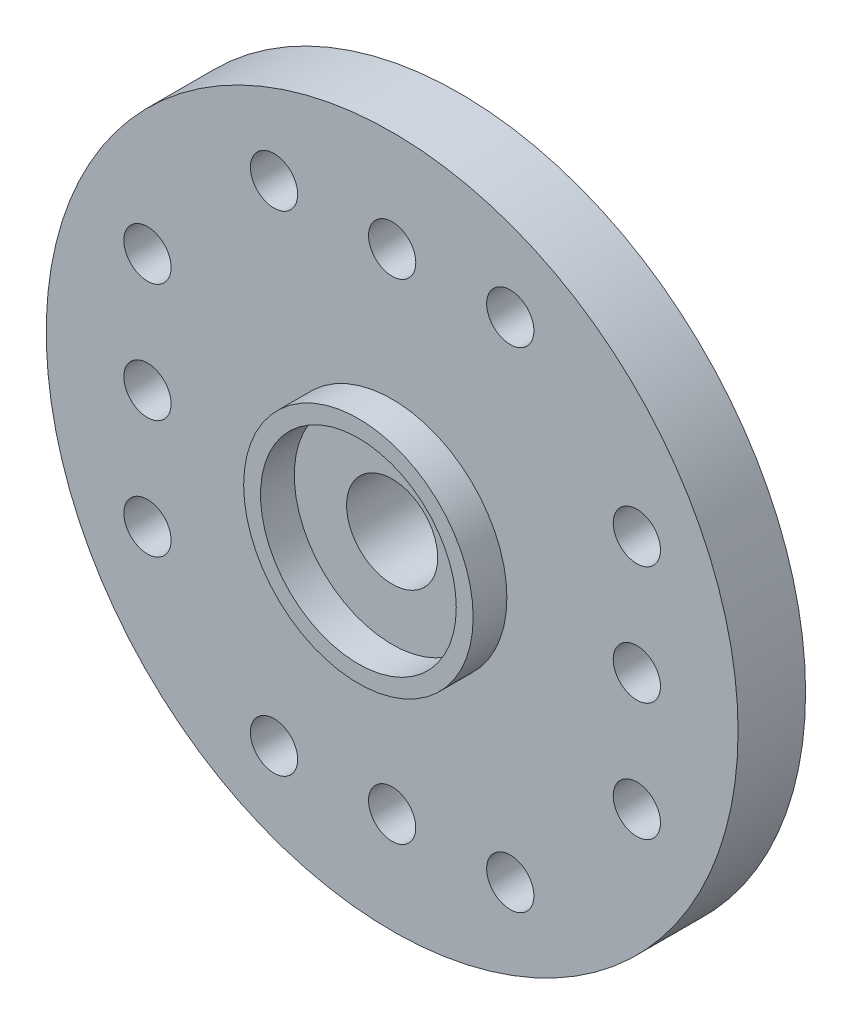
SolidWorks part; units mm, degrees
ref_plane "Front Plane" through (0, 0, 0) normal (0, 0, 1) x (1, 0, 0)
ref_plane "Top Plane" through (0, 0, 0) normal (0, 1, 0) x (1, 0, 0)
ref_plane "Right Plane" through (0, 0, 0) normal (1, 0, 0) x (0, 0, -1)
sketch "Sketch1" plane through (0, 0, 0) normal (0, 0, 1) x (1, 0, 0)
  circle A0 centre (0, 0) radius 10.25
  dimension "D1" = 20.5
extrude "Boss-Extrude1" add sketch "Sketch1" along normal blind 2
sketch "Sketch2" plane through (0, 0, 2) normal (0, 0, 1) x (1, 0, 0)
  circle A0 centre (0, 0) radius 3.4
  circle A1 centre (0, 0) radius 2.9
  dimension "D1" = 6.8
  dimension "D2" = 5.8
extrude "Boss-Extrude2" add sketch "Sketch2" along normal blind 1
sketch "Sketch3" plane through (0, 0, 2) normal (0, 0, 1) x (1, 0, 0)
  circle A0 centre (0, 0) radius 1.35
  dimension "D1" = 2.7
extrude "Cut-Extrude1" cut sketch "Sketch3" against normal through all
sketch "Sketch4" plane through (0, 0, 2) normal (0, 0, 1) x (1, 0, 0)
  line L0 (0, 7.25) -> (0, 0) construction
  line L1 (0, 0) -> (5.2765, 0) construction
  circle A0 centre (0, 7.25) radius 0.7
  circle A1 centre (3.5, 7.25) radius 0.7
  circle A2 centre (-3.5, 7.25) radius 0.7
  circle A3 centre (-3.5, -7.25) radius 0.7
  circle A4 centre (3.5, -7.25) radius 0.7
  circle A5 centre (0, -7.25) radius 0.7
  dimension "D1" = 1.4
  dimension "D2" = 14.5
  dimension "D3" = 7
extrude "Cut-Extrude2" cut sketch "Sketch4" against normal through all
ref_axis "Axis1" through (0, 0, 2) along (0, 0, -1)
pattern_circular "CirPattern1" count 4 over 360 about axis through (0, 0, 2) along (0, 0, -1) of "Cut-Extrude2"
sketch "Sketch5" plane through (0, 0, 0) normal (0, 0, -1) x (-1, 0, 0)
  circle A0 centre (0, 0) radius 2.7
  circle A1 centre (0, 0) radius 4.85
  dimension "D1" = 9.7
  dimension "D2" = 5.4
extrude "Boss-Extrude3" add sketch "Sketch5" along normal blind 3
